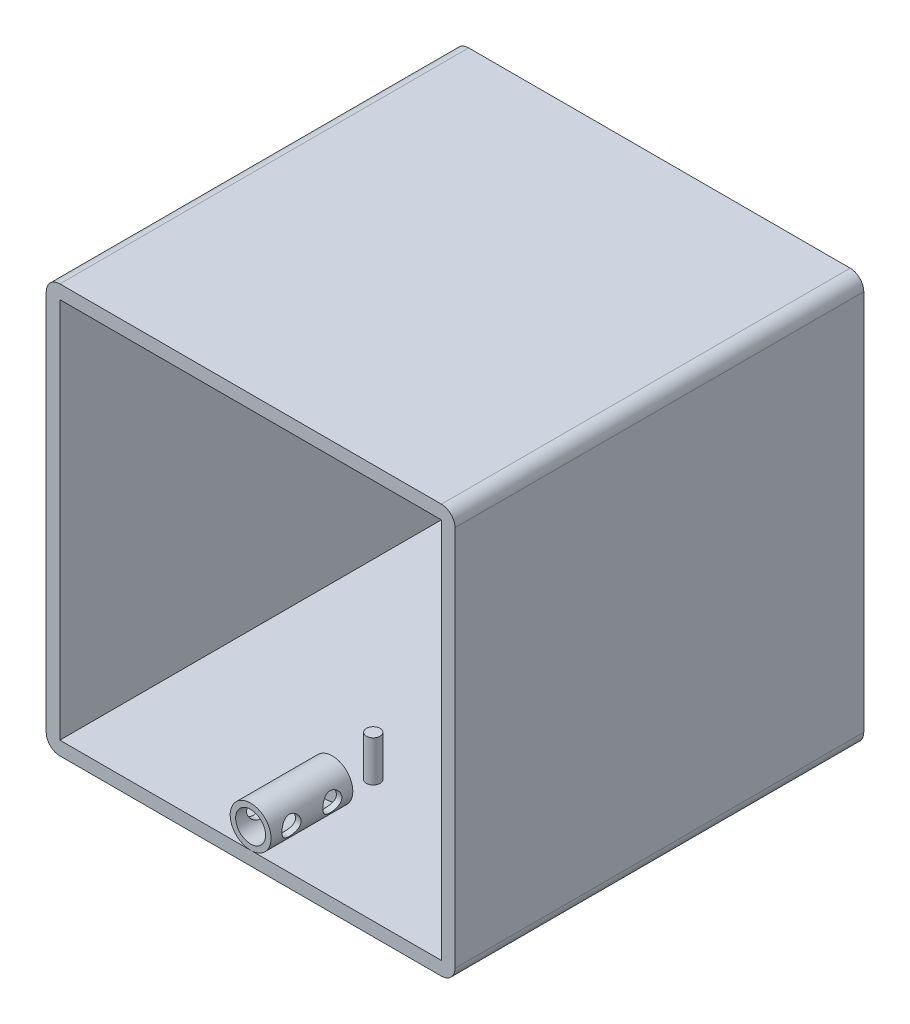
SolidWorks part; units mm, degrees
material "Balsa"
ref_plane "Front Plane" through (0, 0, 0) normal (0, 0, 1) x (1, 0, 0)
ref_plane "Top Plane" through (0, 0, 0) normal (0, 1, 0) x (1, 0, 0)
ref_plane "Right Plane" through (0, 0, 0) normal (1, 0, 0) x (0, 0, -1)
sketch "Sketch1" plane through (0, 0, 0) normal (0, 0, 1) x (1, 0, 0)
  line L1 (-140, -150) -> (140, -150)
  line L2 (-150, -140) -> (-150, 140)
  line L3 (-140, 150) -> (140, 150)
  line L4 (150, -140) -> (150, 140)
  line L5 (-150, -150) -> (150, 150) construction
  line L6 (-150, 150) -> (150, -150) construction
  arc A0 (-140, 150) -> (-150, 140) centre (-140, 140) ccw
  arc A1 (-140, -150) -> (-150, -140) centre (-140, -140) cw
  arc A2 (150, -140) -> (140, -150) centre (140, -140) cw
  arc A3 (150, 140) -> (140, 150) centre (140, 140) ccw
  point P0 (0, 0)
  dimension "D3" = 10
  dimension "D4" = 10
  dimension "D5" = 10
  dimension "D6" = 10
  dimension "D1" = 300
  dimension "D2" = 300
extrude "Boss-Extrude1" add sketch "Sketch1" along normal blind 300
shell "Shell1" thickness 10 removed face at (0, 0, 300)
sketch "Sketch2" plane through (0, 0, 0) normal (0, 0, 1) x (1, 0, 0)
  line L2 (-140, -140) -> (140, -140) construction
  circle A0 centre (0, -125) radius 15
  dimension "D1" = 30
extrude "Boss-Extrude2" add sketch "Sketch2" along normal blind 60 from offset 240 separate body
shell "Shell2" thickness 4 removed face at (15, -125, 300)
sketch "Sketch4" plane through (0, 0, 0) normal (1, 0, 0) x (0, 0, -1)
  line L0 (-300, -140) -> (-300, 140) construction
  line L1 (-300, -150) -> (0, -150) construction
  circle A0 centre (-285, -125) radius 7
  circle A1 centre (-255, -125) radius 7
  dimension "D3" = 14
  dimension "D4" = 14
  dimension "D1" = 15
  dimension "D2" = 45
  dimension "D5" = 25
  dimension "D6" = 25
extrude "Cut-Extrude1" cut sketch "Sketch4" against normal blind 60 and the other way blind 60
sketch "Sketch7" plane through (0, -140, 0) normal (0, 1, 0) x (1, 0, 0)
  line L0 (-150, -300) -> (-150, 0) construction
  line L1 (140, -300) -> (-140, -300) construction
  circle A0 centre (0, -210) radius 5
  dimension "D3" = 10
  dimension "D1" = 150
  dimension "D2" = 90
extrude "Boss-Extrude3" add sketch "Sketch7" along normal blind 30
